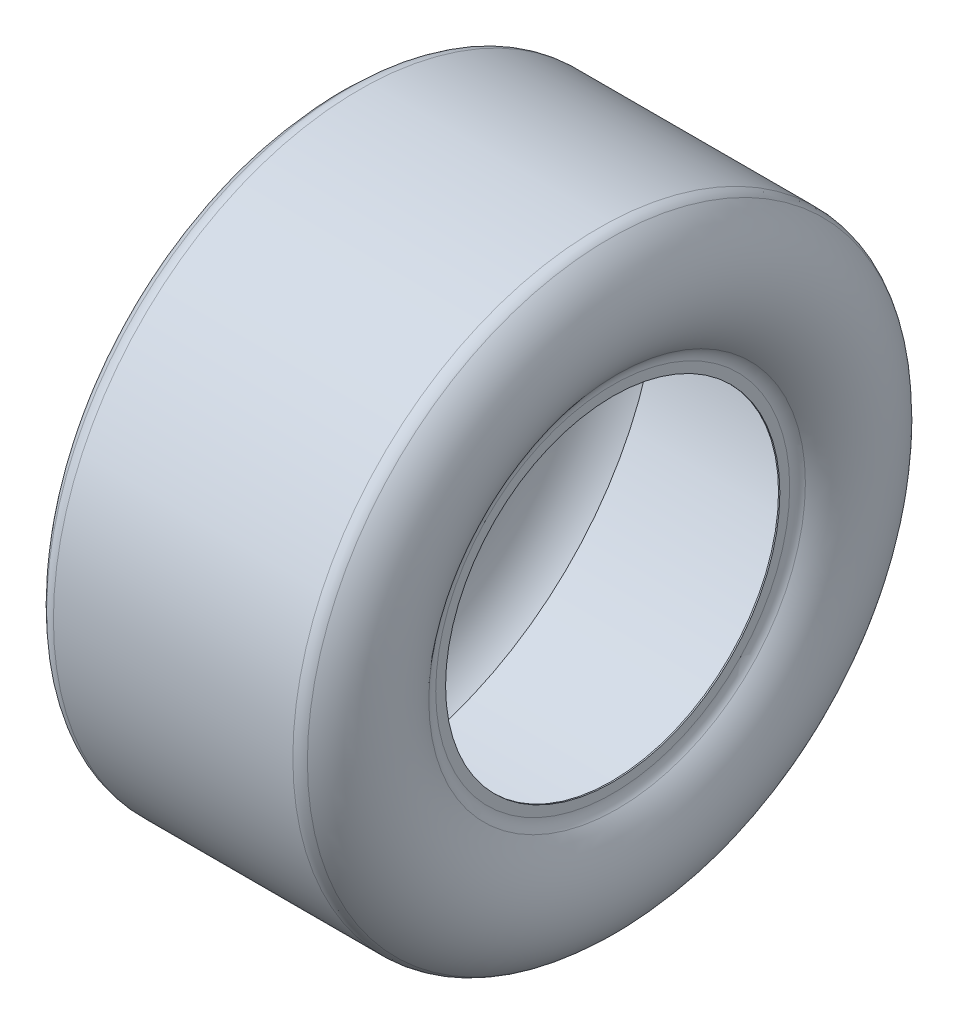
SolidWorks part; units mm, degrees
material "Silicon Rubber"
ref_plane "Front Plane" through (0, 0, 0) normal (0, 0, 1) x (1, 0, 0)
ref_plane "Top Plane" through (0, 0, 0) normal (0, 1, 0) x (1, 0, 0)
ref_plane "Right Plane" through (0, 0, 0) normal (1, 0, 0) x (0, 0, -1)
sketch "Sketch1" plane through (0, 0, 0) normal (0, 0, 1) x (1, 0, 0)
  line L0 (0, 0) -> (0, 232.41)
  line L1 (-101.6, 127) -> (0, 127)
  line L2 (0, 232.41) -> (-95.25, 232.41)
  line L3 (-120.65, 183.4793) -> (0, 183.4793)
  line L4 (0, 0) -> (-205.0641, 0)
  line L5 (-101.6, 139.7) -> (-101.6, 127)
  arc A0 (-101.6, 139.7) -> (-95.25, 232.41) centre (-60.8198, 183.4793) cw
  dimension "D1" = 232.41
  dimension "D2" = 101.6
  dimension "D3" = 127
  dimension "D4" = 95.25
  dimension "D5" = 120.65
  dimension "D6" = 12.7
revolve "Revolve1" add sketch "Sketch1" angle 360 about L4 region at (-56.144, 156.2811, 0) region at (-56.7625, 207.085, 0)
mirror "Mirror1" about plane through (0, 0, 0) normal (1, 0, 0) of "Revolve1"
shell "Shell1" thickness 1.016 removed face at (-101.6, 0, -127)
fillet "Fillet1" radius 12.7 4 edges at (-95.25, 0, -232.41) (95.25, 0, -232.41) (101.6, 0, -139.7) (-101.6, 0, -139.7)
